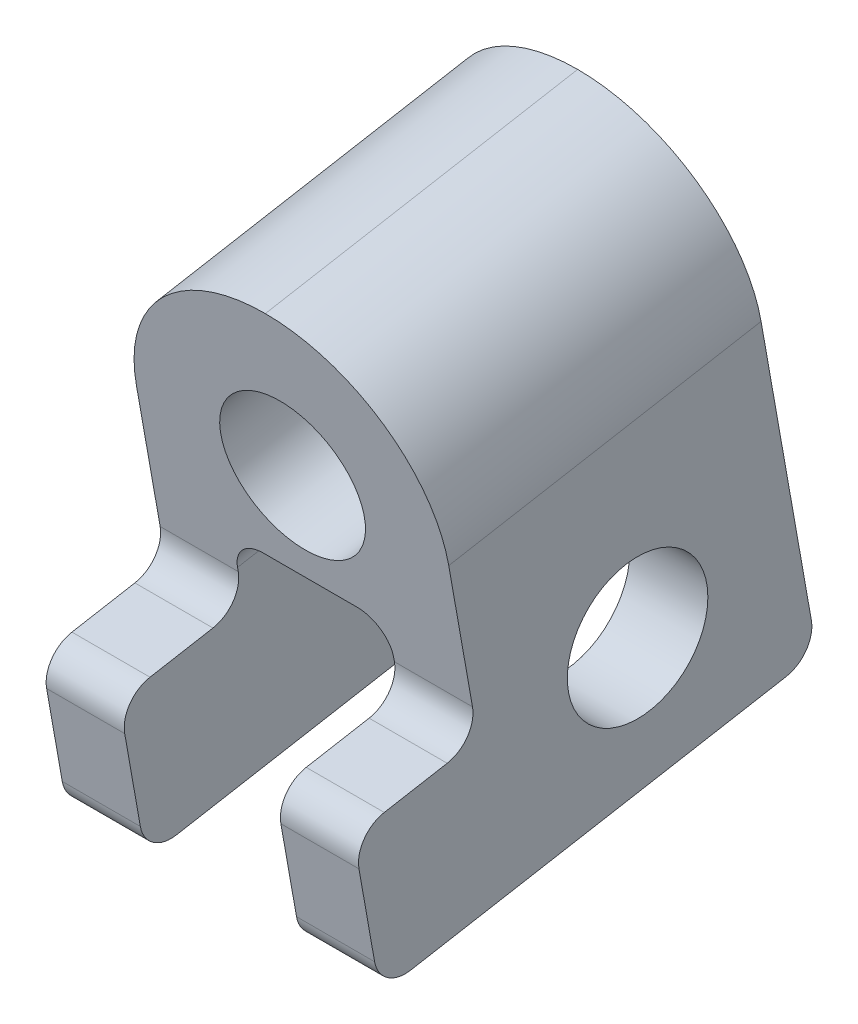
SolidWorks part; units mm, degrees
material "ABS"
ref_plane "Alzado" through (0, 0, 0) normal (0, 0, 1) x (1, 0, 0)
ref_plane "Planta" through (0, 0, 0) normal (0, 1, 0) x (1, 0, 0)
ref_plane "Vista lateral" through (0, 0, 0) normal (1, 0, 0) x (0, 0, -1)
sketch "Croquis2" plane through (0, 0, 0) normal (1, 0, 0) x (0, 0, -1)
  line L0 (267.692, 425.6511) -> (162.455, 393.633) construction
  line L1 (130.6997, 302.8032) -> (132.5066, 292.5986)
  line L2 (132.5066, 292.5986) -> (128.5229, 291.8932)
  line L3 (128.5229, 291.8932) -> (129.3719, 287.0978)
  line L4 (129.3719, 287.0978) -> (143.3556, 289.5738)
  line L5 (143.3556, 289.5738) -> (140.6997, 304.5738)
  line L6 (140.6997, 304.5738) -> (130.6997, 302.8032)
  dimension "D1" = 110
  dimension "D2" = 10
  dimension "D3" = 15
extrude "Saliente-Extruir1" add sketch "Croquis2" along normal blind 10
sketch "Croquis3" plane through (0, 31.6427, -178.7115) normal (0, -0.1743, 0.9847) x (1, 0, 0)
  line L0 (5, 275.3782) -> (5, 265.0148) construction
  line L1 (10, 275.3782) -> (0, 275.3782) construction
  line L2 (10, 265.0148) -> (0, 265.0148) construction
  circle A0 centre (5, 270.3782) radius 2.3
  dimension "D1" = 4.6
  dimension "D2" = 5
extrude "Cortar-Extruir1" cut sketch "Croquis3" against normal through all
fillet "Redondeo1" radius 5 2 edges at (10, 303.6885, -135.6997) (0, 303.6885, -135.6997)
sketch "Croquis4" plane through (10, 0, 0) normal (1, 0, 0) x (0, 0, -1)
  line L1 (136.5715, 298.7651) -> (138.3556, 288.6885) construction
  line L2 (141.5715, 299.6504) -> (131.5715, 297.8798) construction
  line L3 (143.3556, 289.5738) -> (141.5715, 299.6504) construction
  line L4 (129.3719, 287.0978) -> (143.3556, 289.5738) construction
  circle A0 centre (137.6176, 292.857) radius 2.25
  point P10 (137.4635, 293.7268)
  dimension "D1" = 4.5
  dimension "D2" = 6
extrude "Cortar-Extruir2" cut sketch "Croquis4" against normal through all
fillet "Redondeo2" radius 1 4 edges at (5, 289.5738, -143.3556) (5, 287.0978, -129.3719) (5, 291.8932, -128.5229) (5, 292.5986, -132.5066)
sketch "Croquis5" plane through (0, 256.1605, 45.3559) normal (0, -0.9847, -0.1743) x (1, 0, 0)
  line L0 (0, -177.4456) -> (10, -177.4456) construction
  line L1 (2.5, -177.4456) -> (7.5, -177.4456)
  line L2 (2.5, -177.4456) -> (2.5, -191.6468)
  line L3 (2.5, -191.6468) -> (7.5, -191.6468)
  line L4 (7.5, -177.4456) -> (7.5, -191.6468)
  line L6 (10, -191.6468) -> (0, -191.6468) construction
  line L7 (5, -191.6468) -> (5, -177.4456) construction
  line L8 (0, -178.4456) -> (0, -190.6468) construction
  line L9 (10, -178.4456) -> (10, -190.6468) construction
  dimension "D1" = 5
extrude "Cortar-Extruir3" cut sketch "Croquis5" against normal blind 7
fillet "Redondeo3" radius 1 2 edges at (7.5, 295.5813, -137.1352) (2.5, 295.5813, -137.1352)
